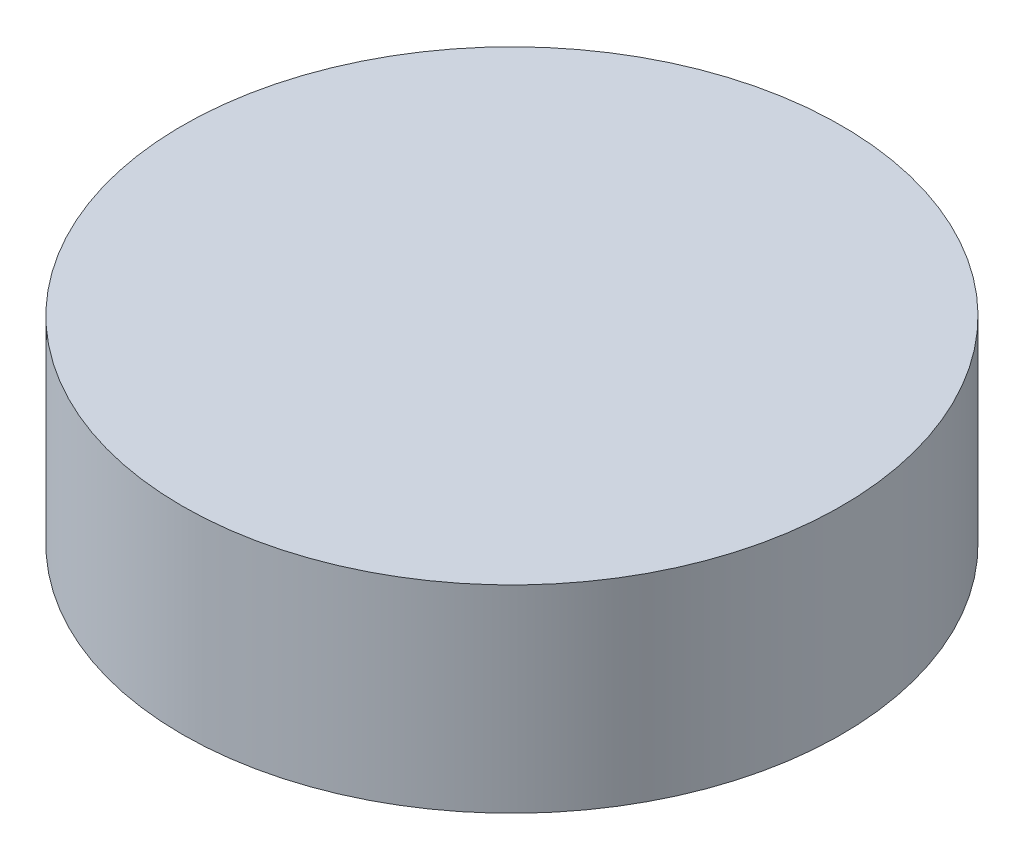
SolidWorks part; units mm, degrees
ref_plane "Front Plane" through (0, 0, 0) normal (0, 0, 1) x (1, 0, 0)
ref_plane "Top Plane" through (0, 0, 0) normal (0, 1, 0) x (1, 0, 0)
ref_plane "Right Plane" through (0, 0, 0) normal (1, 0, 0) x (0, 0, -1)
sketch "Sketch1" plane through (0, 0, 0) normal (0, 1, 0) x (1, 0, 0)
  circle A0 centre (0, 0) radius 25
  dimension "D1" = 50
extrude "Boss-Extrude1" add sketch "Sketch1" along normal mid plane 15
